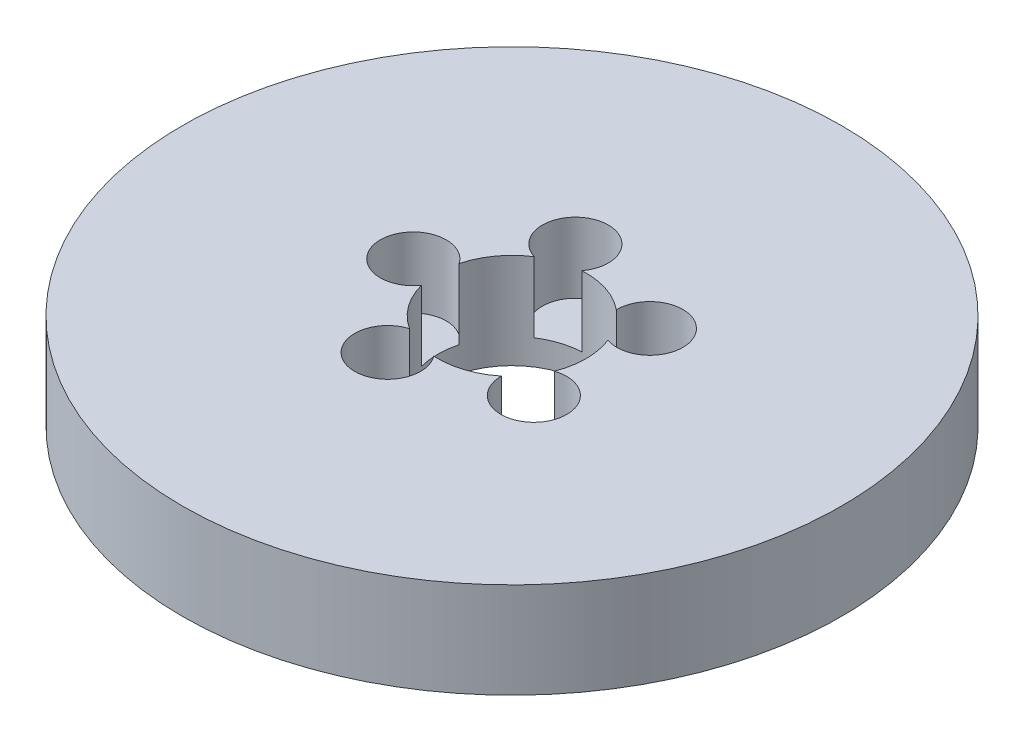
SolidWorks part; units mm, degrees
ref_plane "Front Plane" through (0, 0, 0) normal (0, 0, 1) x (1, 0, 0)
ref_plane "Top Plane" through (0, 0, 0) normal (0, 1, 0) x (1, 0, 0)
ref_plane "Right Plane" through (0, 0, 0) normal (1, 0, 0) x (0, 0, -1)
sketch "Sketch1" plane through (0, 0, 0) normal (0, 1, 0) x (1, 0, 0)
  circle A0 centre (0, 0) radius 100
  dimension "FLANGE_OD" = 200
extrude "Boss-Extrude1" add sketch "Sketch1" along normal blind 29
sketch "Sketch2" plane through (0, 0, 0) normal (0, 1, 0) x (1, 0, 0)
  circle A0 centre (0, 0) radius 22.5
  dimension "BORE_D" = 45
extrude "Cut-Extrude1" cut sketch "Sketch2" along normal through all
sketch "Sketch3" plane through (0, 29, 0) normal (0, 1, 0) x (1, 0, 0)
  circle A0 centre (0, 0) radius 29.9505 construction
  circle A1 centre (-29.9505, 0) radius 10
  dimension "BOLT_D" = 20
  dimension "BOLT_PCD" = 59.901
extrude "Cut-Extrude2" cut sketch "Sketch3" against normal blind 21.3216
pattern_circular "CirPattern1" count 5 over 360 about axis through (0, 0, 0) along (0, 1, 0) of "Cut-Extrude2"
